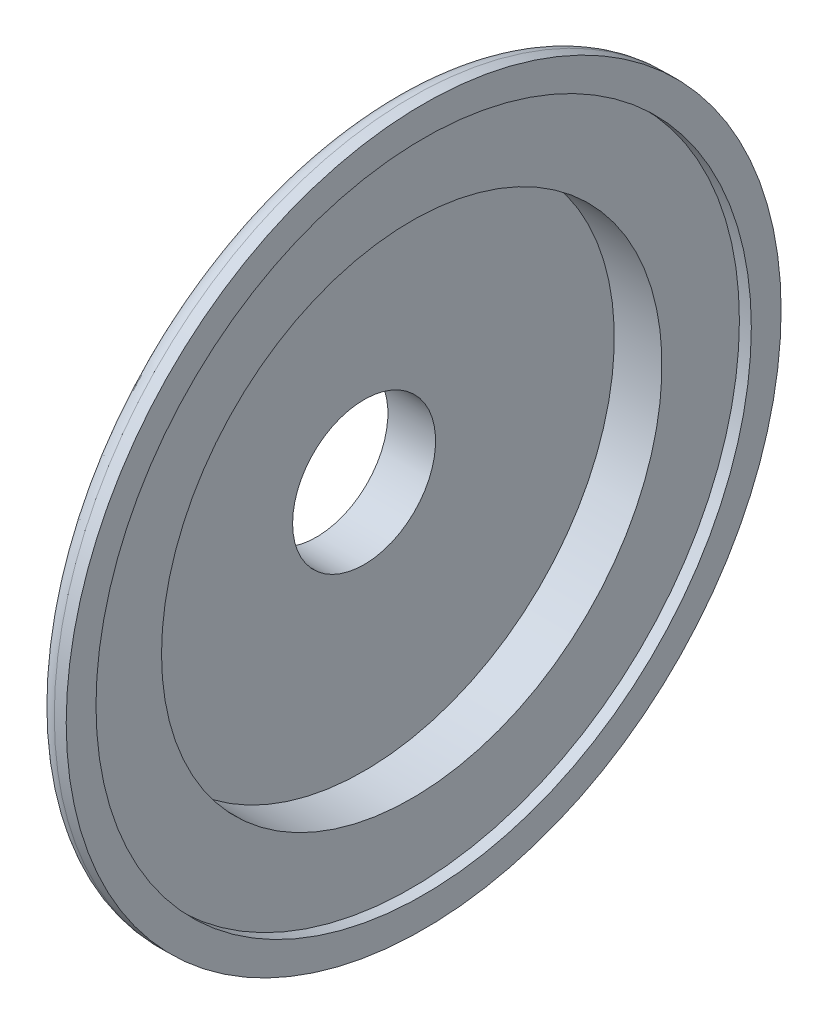
SolidWorks part; units mm, degrees
ref_plane "Front Plane" through (0, 0, 0) normal (0, 0, 1) x (1, 0, 0)
ref_plane "Top Plane" through (0, 0, 0) normal (0, 1, 0) x (1, 0, 0)
ref_plane "Right Plane" through (0, 0, 0) normal (1, 0, 0) x (0, 0, -1)
sketch "Sketch1" plane through (0, 0, 0) normal (0, 0, 1) x (1, 0, 0)
  line L0 (-9, 0) -> (9, 0) construction
  line L1 (9, 60) -> (4, 60)
  line L2 (4, 60) -> (4, 45)
  line L3 (4, 45) -> (-4, 45)
  line L4 (-4, 45) -> (-4, 15)
  line L5 (-4, 15) -> (-9, 15)
  line L6 (-9, 15) -> (-9, 12)
  line L7 (-9, 12) -> (-1, 12)
  line L8 (-1, 12) -> (-1, 42)
  line L9 (-1, 42) -> (7, 42)
  line L10 (7, 42) -> (7, 55)
  line L11 (7, 55) -> (9, 55)
  line L12 (9, 55) -> (9, 60)
  point P3 (7.3858, 42.5308)
  point P4 (0, 0)
  point P13 (0, 0)
  point P18 (9, 53.3845)
  point P19 (4, 45.6813)
  dimension "D1" = 18
  dimension "D2" = 120
  dimension "D3" = 3
  dimension "D4" = 3
  dimension "D5" = 24
  dimension "D6" = 3
  dimension "D7" = 3
  dimension "D8" = 5
  dimension "D9" = 8
  dimension "D10" = 5
  dimension "D11" = 15
revolve "Revolve1" add sketch "Sketch1" angle 360 about L0
fillet "Fillet2" radius 3 3 edges at (-9, 0, 15) (-4, 0, 45) (4, 0, 60)
